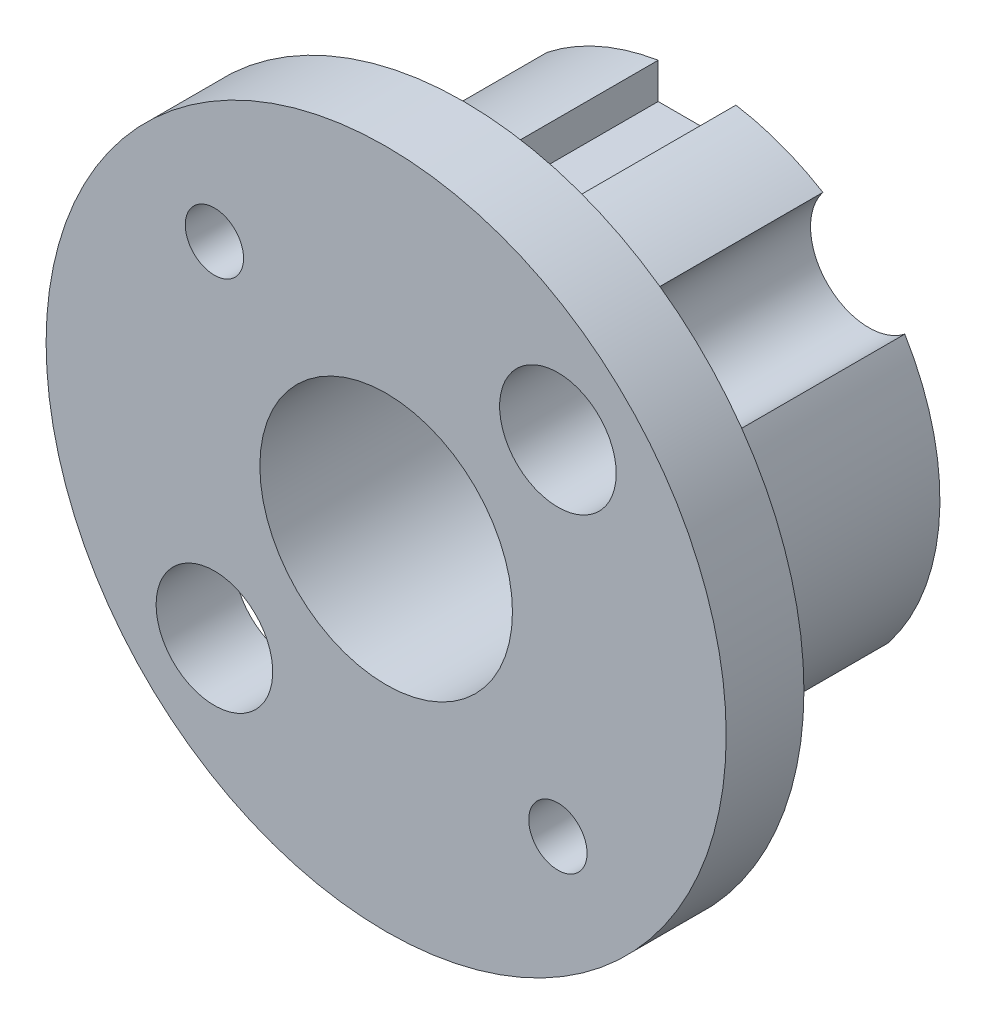
SolidWorks part; units mm, degrees
ref_plane "前视基准面" through (0, 0, 0) normal (0, 0, 1) x (1, 0, 0)
ref_plane "上视基准面" through (0, 0, 0) normal (0, 1, 0) x (1, 0, 0)
ref_plane "右视基准面" through (0, 0, 0) normal (1, 0, 0) x (0, 0, -1)
sketch "草图1" plane through (0, 0, 0) normal (0, 0, 1) x (1, 0, 0)
  circle A0 centre (0, 0) radius 12.5
  dimension "D1" = 25
extrude "拉伸1" add sketch "草图1" along normal blind 12
sketch "草图2" plane through (0, 0, 12) normal (0, 0, 1) x (1, 0, 0)
  line L0 (0, 0) -> (0, 22.7027) construction
  line L1 (-2, -14.2697) -> (2, -14.2697)
  line L2 (-2, 14.5) -> (2, 14.5)
  line L3 (-2, 14.5) -> (-2, 10.5)
  line L4 (-2, 10.5) -> (2, 10.5)
  line L5 (2, 14.5) -> (2, 10.5)
  line L6 (-2, -14.2697) -> (-2, -10.5)
  line L7 (-2, -10.5) -> (2, -10.5)
  line L8 (2, -14.2697) -> (2, -10.5)
  line L9 (0, 0) -> (18.8908, 0) construction
  line L10 (18.8908, 12.5) -> (0, 12.5) construction
  circle A0 centre (0, 0) radius 12.5 construction
  dimension "D1" = 4
  dimension "D2" = 4
extrude "切除-拉伸1" cut sketch "草图2" against normal through all
sketch "草图3" plane through (0, 0, 12) normal (0, 0, 1) x (1, 0, 0)
  circle A0 centre (0, 0) radius 6.5
  dimension "D1" = 13
extrude "切除-拉伸2" cut sketch "草图3" against normal through all
sketch "草图5" plane through (0, 0, 12) normal (0, 0, -1) x (-1, 0, 0)
  circle A0 centre (0, 0) radius 17.5
  dimension "D1" = 35
extrude "凸台-拉伸1" add sketch "草图5" against normal blind 4
sketch "草图4" plane through (0, 0, 16) normal (0, 0, 1) x (1, 0, 0)
  line L0 (0, 0) -> (14.69, 0) construction
  line L1 (0, 0) -> (10.7497, 10.7497) construction
  line L2 (0, 0) -> (-8.6111, 8.6111) construction
  circle A0 centre (0, 0) radius 12.5 construction
  circle A1 centre (8.8388, 8.8388) radius 3
  circle A2 centre (-8.8388, 8.8388) radius 1.5
  circle A3 centre (-8.8388, -8.8388) radius 3
  circle A4 centre (8.8388, -8.8388) radius 1.5
  circle A5 centre (0, 0) radius 6.5 construction
  circle A6 centre (0, 0) radius 6.5
  dimension "D1" = 25
  dimension "D3" = 3
  dimension "D4" = 6
  dimension "D2" = 45
extrude "切除-拉伸3" cut sketch "草图4" against normal through all
fillet "圆角2" radius 2 4 edges at (-2, -11.4195, 12) (2, -11.4195, 12) (2, 11.4195, 12) (-2, 11.4195, 12)
